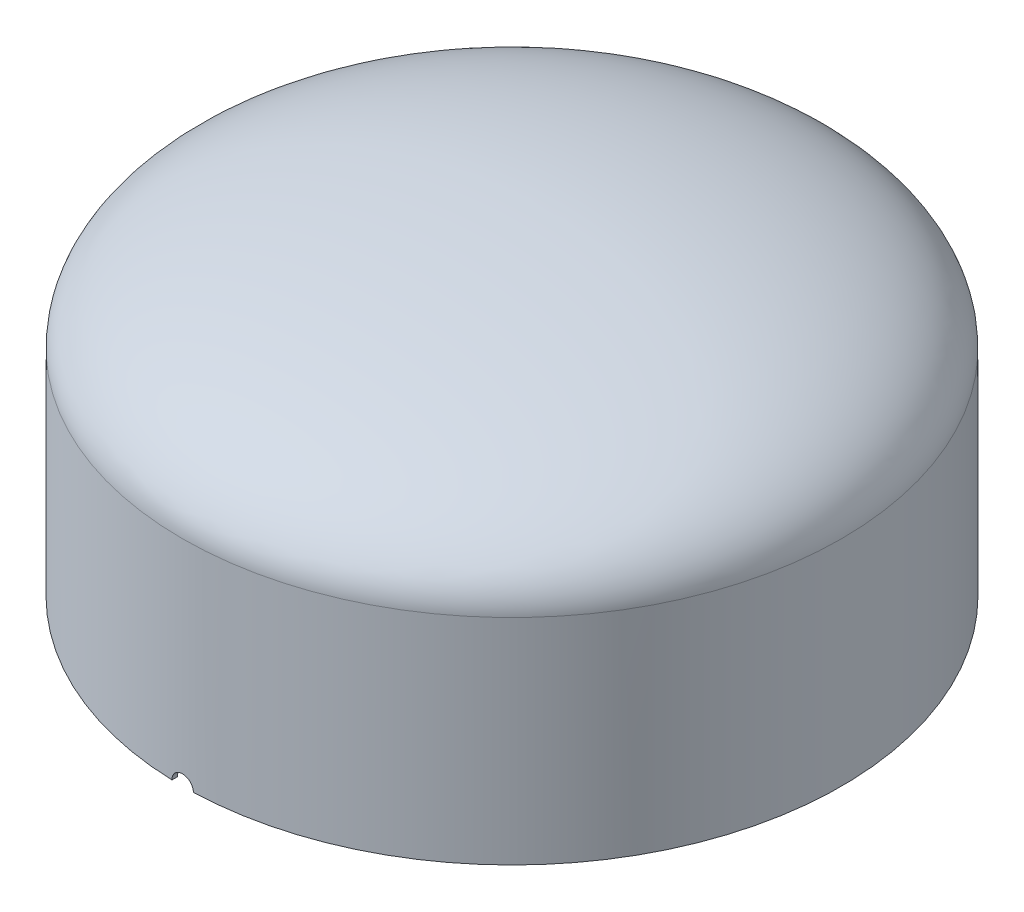
SolidWorks part; units mm, degrees
ref_plane "Front Plane" through (0, 0, 0) normal (0, 0, 1) x (1, 0, 0)
ref_plane "Top Plane" through (0, 0, 0) normal (0, 1, 0) x (1, 0, 0)
ref_plane "Right Plane" through (0, 0, 0) normal (1, 0, 0) x (0, 0, -1)
sketch "Sketch1" plane through (0, 0, 0) normal (0, 0, 1) x (1, 0, 0)
  line L0 (0, 52.5563) -> (0, 55.0963)
  line L2 (0, 0) -> (0, 34.8608) construction
  line L3 (156.21, 0) -> (156.21, -101.6)
  line L4 (153.67, 0) -> (153.67, -101.6)
  line L5 (153.67, -101.6) -> (156.21, -101.6)
  ellipse E0 centre (0, 0) end of major axis (-153.67, 0) minor radius 52.5563 (153.67, 0) -> (0, 52.5563) ccw
  spline S1 degree 3 poles (156.21, 0) (156.21, 1.9624) (155.6425, 5.8873) (152.334, 13.4729) (144.4751, 22.2601) (129.7324, 31.6705) (110.1708, 39.8164) (86.4827, 46.4615) (50.5594, 53.0309) (20.2238, 55.0963) (0, 55.0963) knots 3.141593 3.141593 3.141593 3.141593 3.239767 3.337942 3.534292 3.730641 3.926991 4.12334 4.31969 4.712389 4.712389 4.712389 4.712389
  dimension "D1" = 52.5563
  dimension "D2" = 153.67
  dimension "D3" = 101.6
revolve "Revolve1" add sketch "Sketch1" angle 360 about L2
sketch "Sketch2" plane through (0, 0, 0) normal (0, 0, 1) x (1, 0, 0)
  line L0 (-156.21, -101.6) -> (156.21, -101.6) construction
  circle A0 centre (0, -101.6) radius 5.08
extrude "Cut-Extrude1" cut sketch "Sketch2" against normal blind 157.734 and the other way blind 165.862
